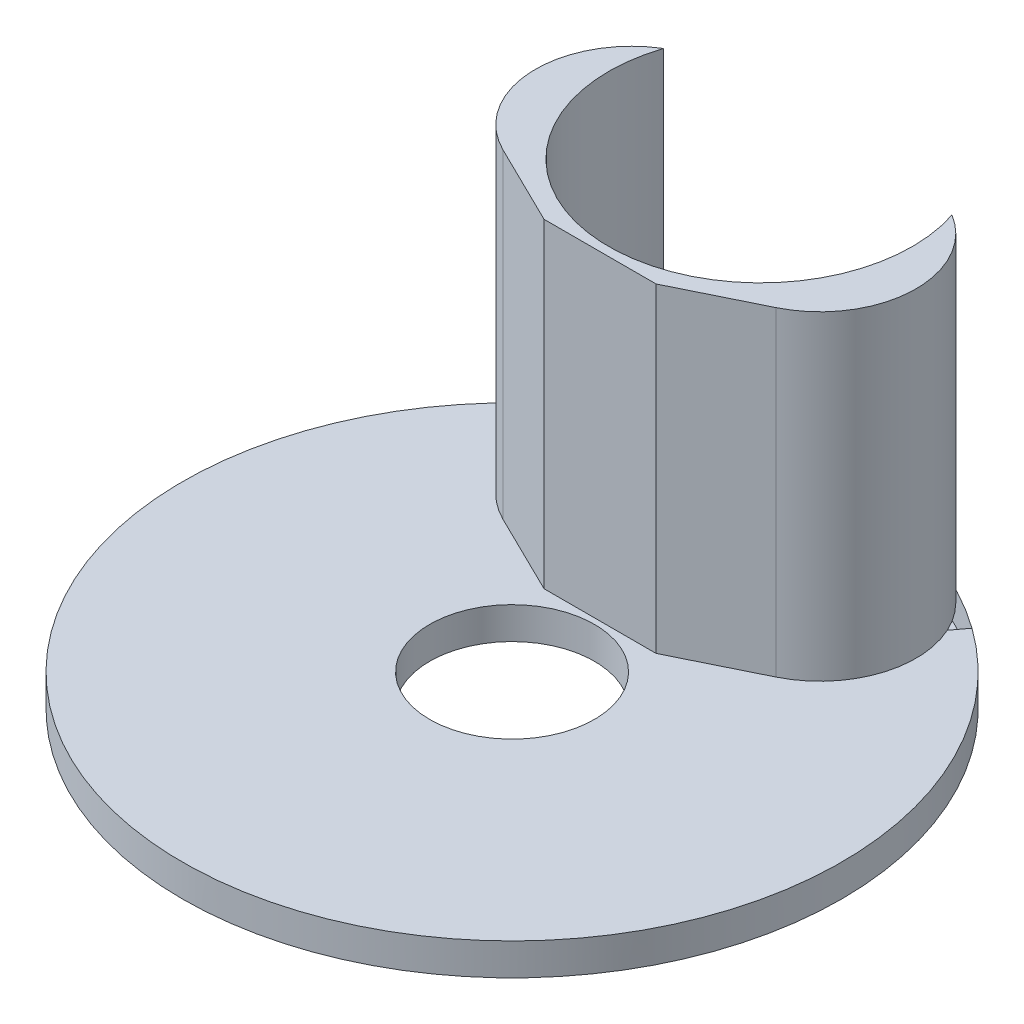
SolidWorks part; units mm, degrees
ref_plane "Front Plane" through (0, 0, 0) normal (0, 0, 1) x (1, 0, 0)
ref_plane "Top Plane" through (0, 0, 0) normal (0, 1, 0) x (1, 0, 0)
ref_plane "Right Plane" through (0, 0, 0) normal (1, 0, 0) x (0, 0, -1)
sketch "Sketch1" plane through (0, 0, 0) normal (0, 1, 0) x (1, 0, 0)
  circle A0 centre (0, 0) radius 20.6
  dimension "D1" = 41.2
extrude "Boss-Extrude1" add sketch "Sketch1" along normal blind 2
sketch "Sketch2" plane through (0, 2, 0) normal (0, 1, 0) x (1, 0, 0)
  circle A0 centre (0, 0) radius 5.15
  dimension "D1" = 10.3
extrude "Cut-Extrude1" cut sketch "Sketch2" against normal blind 3
sketch "Sketch3" plane through (0, 2, 0) normal (0, 1, 0) x (1, 0, 0)
  circle A0 centre (0, 13) radius 6.5
  dimension "D2" = 13
  dimension "D1" = 13
extrude "Cut-Extrude2" cut sketch "Sketch3" against normal blind 2
sketch "Sketch4" plane through (0, 2, 0) normal (0, 1, 0) x (1, 0, 0)
  line L0 (-3.5, 5.5) -> (-16.744, 12)
  line L1 (3.5, 5.5) -> (16.744, 12)
  line L4 (-3.5, 5.5) -> (3.5, 5.5)
  arc A0 (-16.744, 12) -> (-9, 18.53) centre (0, 0) cw
  circle A1 centre (0, 0) radius 20.6 construction
  arc A4 (9, 18.53) -> (16.744, 12) centre (0, 0) cw
  arc A6 (-9, 18.53) -> (9, 18.53) centre (0, 15.5297) ccw
  dimension "D1" = 12
  dimension "D2" = 12
  dimension "D3" = 5.5
  dimension "D4" = 5.5
  dimension "D5" = 3.5
  dimension "D6" = 3.5
  dimension "D7" = 9
  dimension "D8" = 9
extrude "Boss-Extrude4" add sketch "Sketch4" along normal blind 20
fillet "Fillet2" radius 6 2 edges at (16.744, 12, -12) (-16.744, 12, -12)
